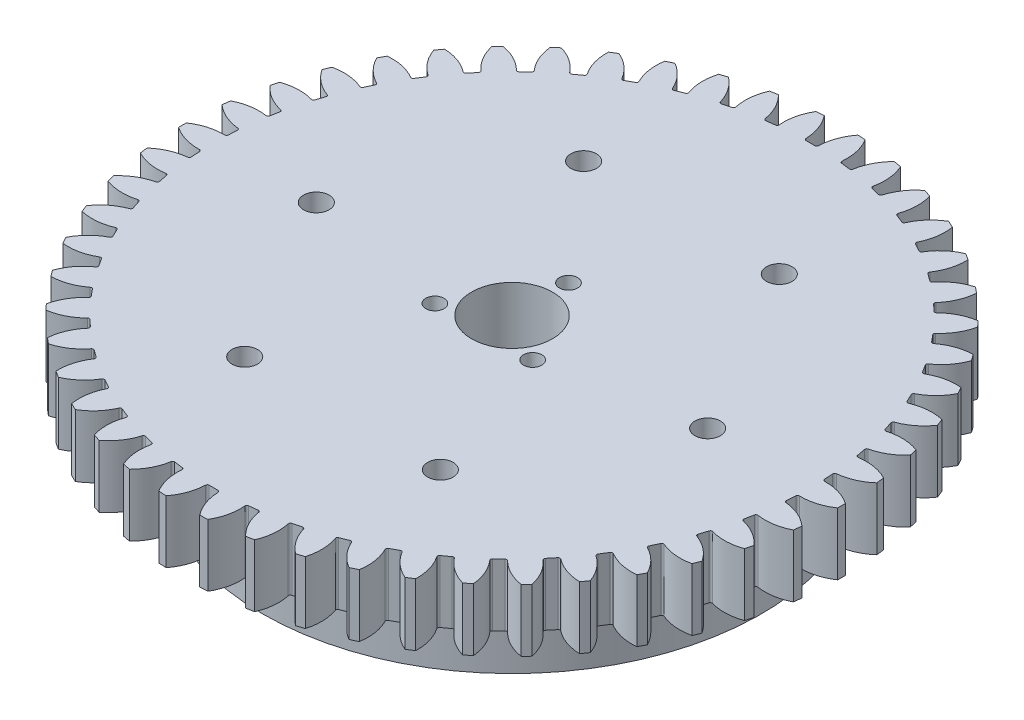
SolidWorks part; units mm, degrees
ref_plane "Front Plane" through (0, 0, 0) normal (0, 0, 1) x (1, 0, 0)
ref_plane "Top Plane" through (0, 0, 0) normal (0, 1, 0) x (1, 0, 0)
ref_plane "Right Plane" through (0, 0, 0) normal (1, 0, 0) x (0, 0, -1)
sketch "Sketch1" plane through (0, 0, 0) normal (0, 1, 0) x (1, 0, 0)
  line L1 (31.4, 0) -> (15.7, 27.1932) construction
  line L2 (15.7, 27.1932) -> (-15.7, 27.1932) construction
  line L3 (-15.7, 27.1932) -> (-31.4, 0) construction
  line L4 (-31.4, 0) -> (-15.7, -27.1932) construction
  line L5 (-15.7, -27.1932) -> (15.7, -27.1932) construction
  line L6 (15.7, -27.1932) -> (31.4, 0) construction
  line L7 (7.85, -4.5322) -> (0, 9.0644) construction
  line L8 (0, 9.0644) -> (-7.85, -4.5322) construction
  line L9 (-7.85, -4.5322) -> (7.85, -4.5322) construction
  circle A1 centre (0, 0) radius 27.1932 construction
  circle A2 centre (-15.7, 27.1932) radius 2.05
  circle A3 centre (15.7, 27.1932) radius 2.05
  circle A4 centre (31.4, 0) radius 2.05
  circle A5 centre (15.7, -27.1932) radius 2.05
  circle A6 centre (-15.7, -27.1932) radius 2.05
  circle A7 centre (-31.4, 0) radius 2.05
  circle A8 centre (0, 0) radius 6.5
  circle A9 centre (0, 0) radius 40
  circle A10 centre (0, 0) radius 4.5322 construction
  circle A11 centre (0, 9.0644) radius 1.55
  circle A12 centre (-7.85, -4.5322) radius 1.55
  circle A13 centre (7.85, -4.5322) radius 1.55
  dimension "D1" = 62.8
  dimension "D2" = 4.1
  dimension "D3" = 80
  dimension "D4" = 13
  dimension "D6" = 3.1
  dimension "D5" = 15.7
extrude "Boss-Extrude2" add sketch "Sketch1" along normal blind 11.5
sketch "Sketch2" plane through (0, 11.5, 0) normal (0, 1, 0) x (1, 0, 0)
  circle A41 centre (0, 0) radius 52.8894
extrude "Boss-Extrude3" add sketch "Sketch2" along normal blind 10 contours A41
extrude "Cut-Extrude1" cut sketch "Sketch1<2>" along normal up to surface (21.5 mm away) from surface contours A7 | A6 | A5 | A4 | A8 | A12 | A13 | A11 | A2 | A3 region at (-15.7, 0, -27.1932) region at (15.7, 0, -27.1932) region at (31.4, 0, 0) region at (15.7, 0, 27.1932) region at (-15.7, 0, 27.1932) region at (-31.4, 0, 0) region at (0, 0, 0) region at (0, 0, -9.0644) region at (-7.85, 0, 4.5322) region at (7.85, 0, 4.5322) up to face at (0, 21.5, 52.8894) starting at face at (0, 11.5, 40)
sketch "Sketch1<2>" plane through (0, 0, 0) normal (0, 1, 0) x (1, 0, 0) same geometry as "Sketch1"
sketch "Sketch3" plane through (0, 21.5, 0) normal (0, 1, 0) x (1, 0, 0)
  line L0 (0, 0) -> (0, 56.5541) construction
  line L1 (0, 52.8894) -> (0, 47.8894)
  line L2 (0.7054, 47.8894) -> (-0.7054, 47.8894)
  line L3 (-9, 55.8894) -> (9, 55.8894)
  circle A0 centre (0, 0) radius 52.8894 construction
  arc A1 (1.0052, 48.1786) -> (9, 55.8894) centre (9, 47.8894) cw
  arc A2 (-1.0052, 48.1786) -> (-9, 55.8894) centre (-9, 47.8894) ccw
  arc A3 (0.7054, 47.8894) -> (1.0052, 48.1786) centre (0.7054, 48.1894) ccw
  arc A4 (-0.7054, 47.8894) -> (-1.0052, 48.1786) centre (-0.7054, 48.1894) cw
  point P11 (0, 47.8894)
  point P15 (1, 47.8894)
  point P18 (-1, 47.8894)
  circle M13 centre (0, 0) radius 52.8894
  dimension "D3" = 8
  dimension "D5" = 0.3
  dimension "D1" = 2
  dimension "D2" = 5
  dimension "D4" = 8
extrude "Cut-Extrude2" cut sketch "Sketch3" against normal up to surface (10 mm away) contours L0 A1 L3 M13 | L2 A3 A1 L1 M13 | A4 L2 L1 A2 M13 | L0 L3 A2 M13 region at (0.8529, 21.5, -50.8369) region at (-2.5467, 21.5, -54.6416) region at (2.5467, 21.5, -54.6416) region at (-0.8529, 21.5, -50.8369) up to face at (0, 11.5, 40)
pattern_circular "CirPattern1" count 50 over 360 about axis through (0, 0, 0) along (0, 1, 0) of "Cut-Extrude2"
extrude "Boss-Extrude4" add sketch "Sketch1<3>" along normal blind 3 contours A12 | A11 | A13 region at (0, 0, -9.0644) region at (-7.85, 0, 4.5322) region at (7.85, 0, 4.5322)
sketch "Sketch1<3>" plane through (0, 0, 0) normal (0, 1, 0) x (1, 0, 0) same geometry as "Sketch1"
chamfer "Chamfer1" distance 20 distance2 1.2 3 edges at (0, 3, -7.5144) (-7.85, 3, 6.0822) (7.85, 3, 6.0822) first distance on face at (0, 3, -7.5144) first distance on face at (-7.85, 3, 6.0822) first distance on face at (7.85, 3, 6.0822)
